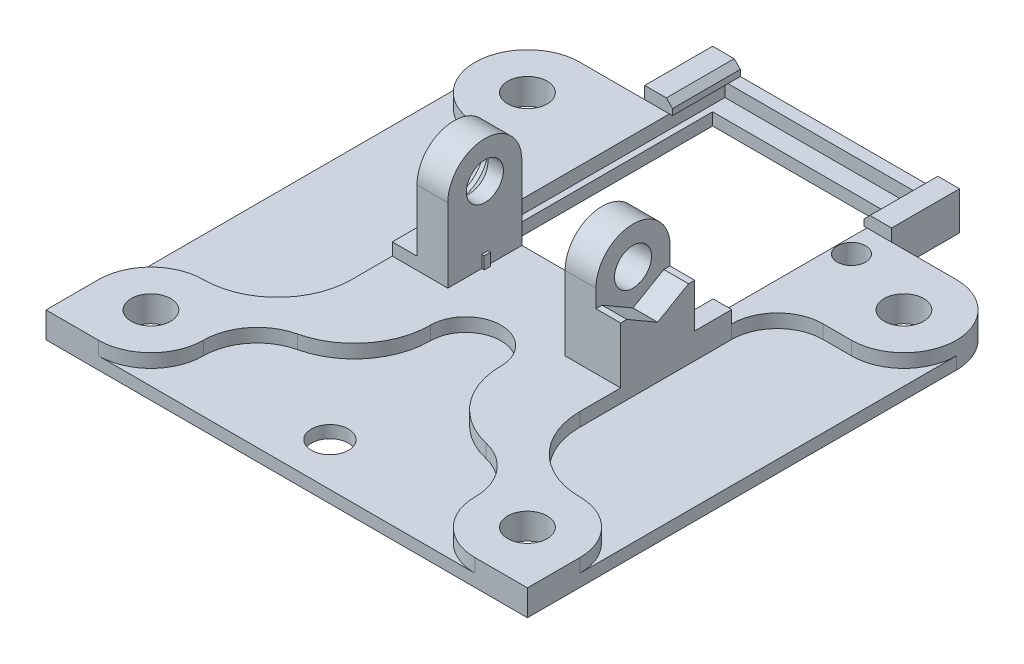
SolidWorks part; units mm, degrees
ref_plane "Front Plane" through (0, 0, 0) normal (0, 0, 1) x (1, 0, 0)
ref_plane "Top Plane" through (0, 0, 0) normal (0, 1, 0) x (1, 0, 0)
ref_plane "Right Plane" through (0, 0, 0) normal (1, 0, 0) x (0, 0, -1)
sketch "Sketch1" plane through (0, 0, 0) normal (0, 1, 0) x (1, 0, 0)
  line L0 (-19.5, 35.2) -> (-19.5, -19.5) construction
  line L1 (-19.5, 19.5) -> (19.5, 19.5)
  line L2 (-19.5, 19.5) -> (-19.5, -19.5)
  line L3 (-19.5, -19.5) -> (19.5, -19.5)
  line L4 (19.5, 19.5) -> (19.5, -19.5)
  line L5 (-19.5, 19.5) -> (19.5, -19.5) construction
  line L6 (-19.5, -19.5) -> (19.5, 19.5) construction
  line L7 (-19.5, -19.5) -> (19.5, -19.5) construction
  line L8 (0, -19.5) -> (0, 19.5) construction
  circle A0 centre (-15.25, -15.25) radius 1.6 construction
  circle A1 centre (15.25, -15.25) radius 1.6 construction
  circle A2 centre (9.2, 17.05) radius 1.15 construction
  circle A3 centre (15.25, 15.25) radius 1.6 construction
  circle A4 centre (-15.25, 15.25) radius 1.6 construction
  circle A5 centre (-15.25, -15.25) radius 1.6
  circle A6 centre (15.25, -15.25) radius 1.6
  circle A7 centre (9.2, 17.05) radius 1.15
  circle A8 centre (15.25, 15.25) radius 1.6
  circle A9 centre (-15.25, 15.25) radius 1.6
  circle A10 centre (-15.25, 15.25) radius 4.25
  circle A11 centre (15.25, 15.25) radius 4.25
  circle A12 centre (-15.25, -15.25) radius 4.25
  circle A13 centre (15.25, -15.25) radius 4.25
  circle A14 centre (0, -16) radius 1.5
  point P0 (0, 0)
  dimension "D1" = 3
  dimension "D2" = 3.5
extrude "Shape" add sketch "Sketch1" along normal blind 2.1 contours A13 L4 A11 L1 A10 L2 A12 L3 A7 | A10 A9 | A11 A8 | A13 A6 | A12 A5 | A12 L2 L3 | A13 L3 L4 region at (-0.0302, 0, -0.0333) region at (-12.3298, 0, -18.1702) region at (18.1702, 0, -18.1702) region at (-18.5507, 0, 18.5507) region at (-15.25, 0, 11.1202) region at (18.1702, 0, 18.1702) region at (18.5507, 0, 18.5507)
sketch "Sketch3" plane through (0, 2.1, 0) normal (0, 1, 0) x (1, 0, 0)
  line L0 (0, 19.5) -> (0, -19.5) construction
  line L1 (-15.25, 19.5) -> (15.25, 19.5) construction
  line L2 (-19.5, -19.5) -> (19.5, -19.5) construction
  line L3 (-19.5, 1.3) -> (19.5, 1.3) construction
  line L4 (-19.5, 15.25) -> (-19.5, -19.5) construction
  line L5 (19.5, 15.25) -> (19.5, -19.5) construction
  line L6 (4.75, 4.3) -> (7.25, 4.3)
  line L7 (-4.75, 4.3) -> (-7.25, 4.3)
  line L8 (-4.75, 4.3) -> (-4.75, -1.7)
  line L9 (-4.75, -1.7) -> (-7.25, -1.7)
  line L10 (-7.25, 4.3) -> (-7.25, -1.7)
  line L11 (-4.75, 4.3) -> (-7.25, -1.7) construction
  line L12 (-4.75, -1.7) -> (-7.25, 4.3) construction
  line L13 (4.75, 4.3) -> (4.75, -1.7)
  line L14 (4.75, -1.7) -> (7.25, -1.7)
  line L15 (7.25, 4.3) -> (7.25, -1.7)
  line L17 (7.25, 4.3) -> (9.25, 4.3)
  line L18 (7.25, 4.3) -> (7.25, -1.7)
  line L19 (7.25, -1.7) -> (9.25, -1.7)
  line L20 (9.25, 4.3) -> (9.25, -1.7)
  point P12 (-6, 1.3)
  dimension "D1" = 18.2
  dimension "D2" = 9.5
  dimension "D3" = 2.5
  dimension "D4" = 6
  dimension "D5" = 4.5
extrude "Supports" add sketch "Sketch3" along normal blind 9 contours L7 L10 L9 L8 | L15 L6 L13 L14 | L20 L17 L15 L19 region at (6, 2.1, -1.3) region at (8.25, 2.1, -1.3) region at (-6, 2.1, -1.3)
sketch "Sketch4" plane through (-7.25, 0, 0) normal (-1, 0, 0) x (0, 0, 1)
  line L0 (-1.3, 11.1) -> (-1.3, 2.1) construction
  line L2 (-4.3, 2.1) -> (1.7, 2.1) construction
  line L3 (1.7, 11.1) -> (1.7, 2.1) construction
  line L4 (-4.3, 11.1) -> (1.7, 11.1) construction
  circle A0 centre (-1.3, 8.1) radius 3
  circle A1 centre (-1.3, 8.1) radius 1.5
  line M2 (1.7, 2.1) -> (1.7, 11.1)
  line M4 (-4.3, 11.1) -> (-4.3, 2.1)
  line M11 (1.7, 11.1) -> (-4.3, 11.1)
  dimension "D1" = 3
extrude "Support cuts" cut sketch "Sketch4" against normal up to surface (16.5 mm away) contours A1 L0 | L0 A1 | A0 M11 M4 | A0 M2 M11 region at (-7.25, 10.4299, 1.0299) region at (-7.25, 10.4299, -3.6299) region at (-7.25, 8.1, -0.6634) region at (-7.25, 8.1, -1.9366) up to face at (9.25, 6.6, -1.3)
sketch "Sketch5" plane through (9.25, 0, 0) normal (1, 0, 0) x (0, 0, -1)
  line L0 (-1.2, 6.6566) -> (-1.7, 6.6566)
  line L1 (1.3, 5.2132) -> (3.8, 6.6566)
  line L2 (3.8, 6.6566) -> (3.8, 9.5434)
  line L3 (3.8, 9.5434) -> (1.3, 10.9868)
  line L4 (1.3, 10.9868) -> (-1.2, 9.5434)
  line L5 (-1.2, 9.5434) -> (-1.2, 6.6566)
  line L6 (-1.2, 6.6566) -> (1.3, 5.2132)
  line L7 (3.8, 6.6566) -> (4.3, 6.6566)
  line L9 (-1.7, 8.1) -> (-1.7, 2.1)
  line L10 (-1.7, 2.1) -> (4.3, 2.1)
  line L11 (4.3, 2.1) -> (4.3, 8.1)
  line L12 (-1.7, 8.1) -> (-1.7, 2.1)
  line L13 (-1.7, 2.1) -> (4.3, 2.1)
  line L14 (4.3, 2.1) -> (4.3, 8.1)
  circle A0 centre (1.3, 8.1) radius 2.5 construction
  circle A1 centre (1.3, 8.1) radius 1.5 construction
  arc A2 (4.3, 8.1) -> (-1.7, 8.1) centre (1.3, 8.1) ccw
  arc A3 (4.3, 8.1) -> (-1.7, 8.1) centre (1.3, 8.1) ccw
  circle M3 centre (1.3, 8.1) radius 1.5
  line M4 (-1.7, 8.1) -> (-1.7, 2.1)
  line M6 (4.3, 2.1) -> (4.3, 8.1)
  arc M7 (4.3, 8.1) -> (-1.7, 8.1) centre (1.3, 8.1) ccw
  dimension "D1" = 5
  dimension "D2" = 0
extrude "Nut holder" cut sketch "Sketch5" against normal blind 2 contours L5 L6 L1 L2 L3 L4 M3 | L2 L7 L0 L5 L4 L3 M6 M7 M4 region at (9.25, 6.7313, 1.45) region at (9.25, 8.1, 1.1236)
sketch "Sketch6" plane through (-7.25, 0, 0) normal (-1, 0, 0) x (0, 0, 1)
  circle A0 centre (-1.3, 8.1) radius 2.4
  dimension "D1" = 4.8
extrude "Screw cut" cut sketch "Sketch6" against normal blind 0.35
chamfer "Scew chamfer" distance 0.9 angle 45 1 edges at (-6.9, 8.1, 0.2)
sketch "Sketch7" plane through (4.75, 0, 0) normal (-1, 0, 0) x (0, 0, 1)
  line L0 (-1.3, 2.1) -> (-1.3, 11.1) construction
  line L1 (-4.3, 2.1) -> (1.7, 2.1) construction
  line L2 (-4.3, 2.1) -> (1.7, 2.1) construction
  line L3 (-1.05, 3.1) -> (-1.55, 3.1)
  line L4 (-1.05, 3.1) -> (-1.05, 2.1)
  line L5 (-1.05, 2.1) -> (-1.55, 2.1)
  line L6 (-1.55, 3.1) -> (-1.55, 2.1)
  line L7 (-1.05, 3.1) -> (-1.55, 2.1) construction
  line L8 (-1.05, 2.1) -> (-1.55, 3.1) construction
  arc A1 (1.7, 8.1) -> (-4.3, 8.1) centre (-1.3, 8.1) ccw construction
  point P7 (-1.3, 2.6)
  dimension "D1" = 0.5
  dimension "D2" = 1
extrude "Angle fix 1" add sketch "Sketch7" along normal blind 0.2
sketch "Sketch8" plane through (-4.75, 0, 0) normal (1, 0, 0) x (0, 0, -1)
  line L4 (1.55, 2.1) -> (1.55, 3.1)
  line L5 (1.05, 2.1) -> (1.55, 2.1)
  line L6 (1.05, 3.1) -> (1.05, 2.1)
  line L7 (1.55, 3.1) -> (1.05, 3.1)
  line L8 (1.55, 2.1) -> (1.55, 3.1)
  line L9 (1.05, 2.1) -> (1.55, 2.1)
  line L10 (1.05, 3.1) -> (1.05, 2.1)
  line L11 (1.55, 3.1) -> (1.05, 3.1)
  dimension "D1" = 0
extrude "Angle fix 2" add sketch "Sketch8" along normal blind 0.2
sketch "Sketch9" plane through (0, 2.1, 0) normal (0, 1, 0) x (1, 0, 0)
  line L0 (8, 4.5) -> (8, 24) construction
  line L1 (8, 24) -> (-8, 24) construction
  line L2 (-8, 24) -> (-8, 4.5) construction
  line L3 (8, 4.5) -> (8, 24)
  line L4 (8, 24) -> (-8, 24)
  line L5 (-8, 24) -> (-8, 4.5)
  line L6 (-15.25, 19.5) -> (15.25, 19.5) construction
  line L7 (-15.25, 19.5) -> (15.25, 19.5)
  line L8 (-8, 24) -> (8, 19.5) construction
  line L9 (-8, 24) -> (8, 24)
  line L14 (10, 25) -> (-10, 25)
  line L15 (10, 25) -> (10, 18.5)
  line L16 (10, 18.5) -> (-10, 18.5)
  line L17 (-10, 25) -> (-10, 18.5)
  line L18 (10, 25) -> (-10, 18.5) construction
  line L19 (10, 18.5) -> (-10, 25) construction
  point P10 (0, 21.75)
  line M5 (15.25, 19.5) -> (-15.25, 19.5)
  dimension "D1" = 1
  dimension "D2" = 2
extrude "Datalogger front" add sketch "Sketch9" against normal up to surface (2.1 mm away) contours L4 L5 L3 M5 | L14 L17 L5 L4 L3 L7 L15 M5 region at (0, 2.1, -21.75) region at (8.2074, 2.1, -21.75) up to face at (0, 0, 17.5)
sketch "Sketch10" plane through (0, 0, -25) normal (0, 0, -1) x (-1, 0, 0)
  line L1 (-8, 2.1) -> (8, 2.1)
  line L2 (-8, 2.1) -> (-8, 1)
  line L3 (-8, 1) -> (8, 1)
  line L4 (8, 2.1) -> (8, 1)
  line L6 (-8, 1) -> (8, 1) construction
  line L8 (8, 2.1) -> (8, 1) construction
extrude "Datalogger main cut" cut sketch "Sketch10" against normal offset from surface (20.7 mm away) 0.2 offset beyond the face yes
sketch "Sketch11" plane through (0, 1, 0) normal (0, 1, 0) x (1, 0, 0)
  line L6 (-7.5, 22.5) -> (7.5, 22.5)
  line L9 (8, 25) -> (-8, 25) construction
  line L12 (-7.5, 4.8) -> (7.5, 4.8)
  line L13 (7.5, 4.8) -> (7.5, 24.5)
  line L14 (7.5, 24.5) -> (-7.5, 24.5)
  line L15 (7.5, 24.5) -> (-7.5, 24.5)
  line L17 (-7.5, 24.5) -> (-7.5, 4.8)
  line L18 (-7.5, 4.8) -> (7.5, 4.8)
  line L19 (7.5, 4.8) -> (7.5, 24.5)
  line L23 (-7.5, 24.5) -> (-7.5, 4.8)
  dimension "D2" = 2.5
  dimension "D1" = 0.5
extrude "Datalogger bottom cut" cut sketch "Sketch11" against normal up to next contours L23 L18 L19 region at (0, 1, -13.65)
sketch "Sketch12" plane through (0, 1, 0) normal (0, 1, 0) x (1, 0, 0)
  line L1 (-8, 25) -> (8, 25)
  line L2 (-8, 25) -> (-8, 24)
  line L3 (-8, 24) -> (8, 24)
  line L4 (8, 25) -> (8, 24)
  dimension "D1" = 1
extrude "Datalogger front retainer" add sketch "Sketch12" along normal up to surface (1.1 mm away) up to face at (0.1333, 2.1, -6.6887)
sketch "Sketch13" plane through (0, 2.1, 0) normal (0, 1, 0) x (1, 0, 0)
  line L1 (-8, 4.3) -> (-9.25, 4.3)
  line L2 (-8, 4.3) -> (-8, 7.3)
  line L3 (-8, 7.3) -> (-9.25, 7.3)
  line L4 (-9.25, 4.3) -> (-9.25, 7.3)
  line L5 (-8, 7.3) -> (-7.75, 7.3)
  line L6 (-8, 7.3) -> (-8, 4.3)
  line L7 (-8, 4.3) -> (-7.75, 4.3)
  line L8 (-7.75, 7.3) -> (-7.75, 4.3)
  line L9 (0, 7.608) -> (0, -4.6396) construction
  line L10 (9.25, 4.3) -> (9.25, 7.3)
  line L11 (8, 7.3) -> (9.25, 7.3)
  line L12 (8, 7.3) -> (7.75, 7.3)
  line L13 (7.75, 7.3) -> (7.75, 4.3)
  line L14 (8, 4.3) -> (7.75, 4.3)
  line L15 (8, 4.3) -> (9.25, 4.3)
  line L16 (-7.25, 4.3) -> (-7.25, -1.7) construction
  line L17 (-9.25, 4.3) -> (-7.25, 4.3)
  line L18 (-9.25, 4.3) -> (-9.25, -1.7)
  line L19 (-9.25, -1.7) -> (-7.25, -1.7)
  line L20 (-7.25, 4.3) -> (-7.25, -1.7)
  line L21 (-4.75, -1.7) -> (-7.25, -1.7) construction
  line L22 (9.25, 4.3) -> (9.25, -1.7) construction
  line M8 (8, 24) -> (8, 4.3)
  line M9 (8, 4.3) -> (9.25, 4.3)
  line M25 (-7.25, 4.3) -> (-8, 4.3)
  line M26 (-8, 4.3) -> (-8, 24)
  line M52 (-7.25, -1.7) -> (-7.25, 4.3)
  dimension "D2" = 3
  dimension "D3" = 0.25
extrude "Datalogger rear retainers" add sketch "Sketch13" along normal blind 1 contours L4 L3 M25 M26 | L8 L5 L7 M26 | L11 L10 M8 M9 | L14 L12 L13 M8 | L18 L19 L1 M52 M25 region at (-8.25, 2.1, -1.3) region at (-8.625, 2.1, -5.8) region at (-7.875, 2.1, -5.8) region at (8.625, 2.1, -5.8) region at (7.875, 2.1, -5.8)
sketch "Sketch14" plane through (0, 2.1, 0) normal (0, 1, 0) x (1, 0, 0)
  line L0 (-15.25, 19.5) -> (-10, 19.5) construction
  line L1 (-10, 25) -> (-7.75, 25)
  line L2 (-10, 25) -> (-10, 19.5)
  line L3 (-10, 19.5) -> (-7.75, 19.5)
  line L4 (-7.75, 25) -> (-7.75, 19.5)
  line L5 (-8, 4.3) -> (-8, 24) construction
  line L8 (0, 25) -> (0, -19.5) construction
  line L9 (10, 25) -> (-10, 25) construction
  line L10 (-19.5, -19.5) -> (19.5, -19.5) construction
  line L11 (10, 25) -> (10, 19.5)
  line L12 (10, 25) -> (7.75, 25)
  line L13 (7.75, 25) -> (7.75, 19.5)
  line L14 (10, 19.5) -> (7.75, 19.5)
  line M43 (10, 19.5) -> (10, 25)
  line M45 (10, 25) -> (-10, 25)
  line M46 (8, 24) -> (8, 7.3)
  line M68 (-8, 7.3) -> (-8, 24)
  line M71 (-10, 25) -> (-10, 19.5)
  line M161 (-8, 24) -> (8, 24)
  dimension "D1" = 0.25
extrude "Datalogger side retainers" add sketch "Sketch14" along normal up to surface (1 mm away) contours M45 M161 M46 M43 | M71 M68 M161 | L4 L3 M161 M68 | L14 L13 M46 M161 region at (-8.975, 2.1, -22.3) region at (-7.875, 2.1, -21.75) region at (8.975, 2.1, -22.3) region at (7.875, 2.1, -21.75) up to face at (-8.0833, 3.1, -3.3)
sketch "Sketch15" plane through (0, 0, -25) normal (0, 0, -1) x (-1, 0, 0)
  line L0 (-7.75, 2.6) -> (-8.25, 3.1)
  line L1 (-7.75, 3.1) -> (-7.75, 2.1) construction
  line L3 (-8.25, 3.1) -> (-7.75, 3.1)
  line L4 (-7.75, 3.1) -> (-7.75, 2.6)
  line L5 (0, 0) -> (0, 2.1) construction
  line L6 (-7.75, 2.1) -> (7.75, 2.1) construction
  line L7 (8.25, 3.1) -> (7.75, 3.1)
  line L8 (7.75, 3.1) -> (7.75, 2.6)
  line L9 (7.75, 2.6) -> (8.25, 3.1)
  dimension "D1" = 45
extrude "Datalogger side retainer clips" cut sketch "Sketch15" against normal up to next
sketch "Sketch16" plane through (0, 2.1, 0) normal (0, 1, 0) x (1, 0, 0)
  line L0 (-19.5, 15.25) -> (-19.5, -19.5) construction
  line L1 (-15.25, 11) -> (-15.25, -11) construction
  line L2 (0, -2.1397) -> (-2.8603, -2.1397) construction
  line L3 (0, 25) -> (0, -19.5) construction
  line L4 (7.75, 25) -> (-7.75, 25) construction
  line L5 (-19.5, -19.5) -> (19.5, -19.5) construction
  line L6 (-15.25, -11) -> (0, -11) construction
  line L7 (-11, -15.25) -> (0, -15.25) construction
  line L8 (-2.8603, 25) -> (-2.8603, -19.5) construction
  line L10 (-9.25, 7.3) -> (-9.25, 19.5) construction
  line L11 (-10, 19.5) -> (-8, 19.5) construction
  line L12 (-19.5, 15.25) -> (-19.5, -15.25)
  line L13 (-9.25, -1.7) -> (-9.25, -11) construction
  line L14 (-9.25, -5) -> (0, -5) construction
  line L15 (-15.25, 11) -> (-9.25, 11) construction
  line L16 (-9.25, 7.3) -> (-9.25, -5)
  line L18 (9.25, 7.3) -> (9.25, -5)
  line L19 (-15.25, -19.5) -> (15.25, -19.5)
  line L20 (15.25, 11) -> (12.95, 11)
  line L22 (-15.25, 11) -> (-12.95, 11)
  circle A0 centre (-15.25, 15.25) radius 4.25
  circle A1 centre (-15.25, -15.25) radius 4.25
  arc A2 (-15.25, 19.5) -> (-19.5, 15.25) centre (-15.25, 15.25) ccw construction
  arc A3 (-9.25, 7.3) -> (-12.95, 11) centre (-12.95, 7.3) ccw
  arc A4 (-15.25, -11) -> (-9.25, -5) centre (-15.25, -5) ccw
  arc A5 (-11, -15.25) -> (-7.625, -11) centre (-6.6366, -15.25) cw
  arc A6 (-7.625, -11) -> (-2.8603, -5) centre (-9.0204, -5) ccw
  arc A7 (-2.8603, -5) -> (2.8603, -5) centre (0, -5) cw
  arc A8 (7.625, -11) -> (2.8603, -5) centre (9.0204, -5) cw
  arc A9 (11, -15.25) -> (7.625, -11) centre (6.6366, -15.25) ccw
  circle A10 centre (15.25, -15.25) radius 4.25
  arc A11 (15.25, -11) -> (9.25, -5) centre (15.25, -5) cw
  arc A12 (9.25, 7.3) -> (12.95, 11) centre (12.95, 7.3) cw
  circle A13 centre (15.25, 15.25) radius 4.25
  line M39 (-19.5, 15.25) -> (-19.5, -19.5)
  line M40 (-19.5, -19.5) -> (19.5, -19.5)
  line M41 (19.5, -19.5) -> (19.5, 15.25)
  circle M45 centre (0, -16) radius 1.5
extrude "Weight cut" cut sketch "Sketch16" against normal offset from surface (1.1 mm away) 1 contours A1 A0 M39 | A10 A9 A8 A7 A6 A5 A1 M40 M45 | A13 L18 A10 M41 region at (-14.7085, 2.1, -0.201) region at (0, 2.1, 13.4582) region at (14.7085, 2.1, -0.201) up to face at (15.25, 0, 16.85)
